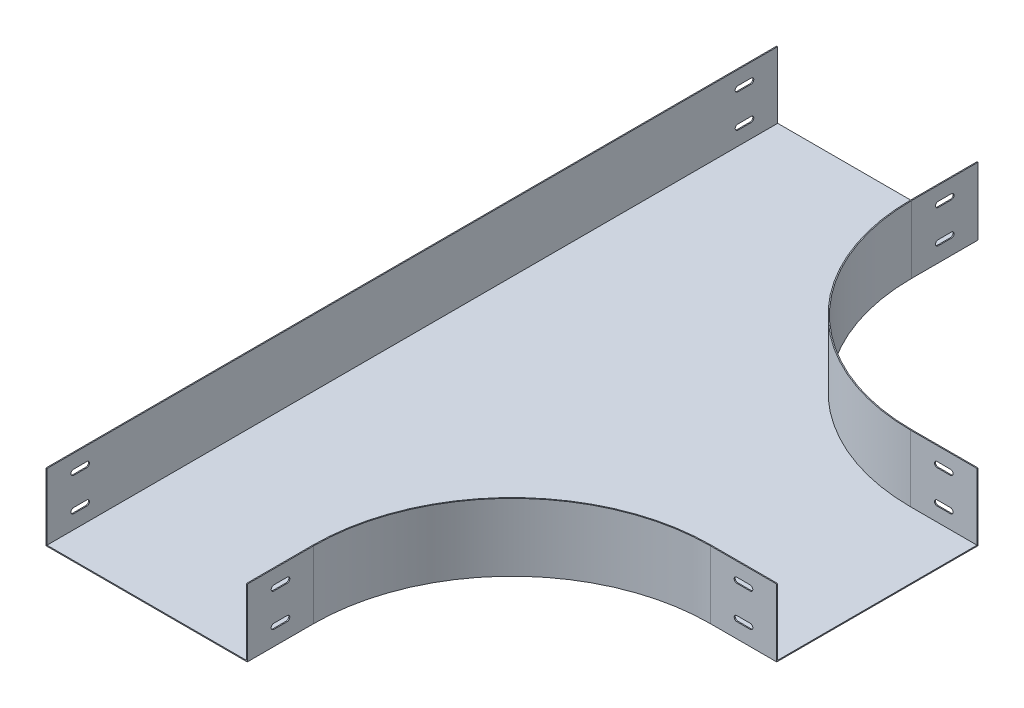
SolidWorks part; units mm, degrees
ref_plane "Front Plane" through (0, 0, 0) normal (0, 0, 1) x (1, 0, 0)
ref_plane "Top Plane" through (0, 0, 0) normal (0, 1, 0) x (1, 0, 0)
ref_plane "Right Plane" through (0, 0, 0) normal (1, 0, 0) x (0, 0, -1)
sketch "Sketch1" plane through (0, 0, 0) normal (0, 1, 0) x (1, 0, 0)
  line L0 (-150, 550) -> (150, 550)
  line L1 (-150, -550) -> (150, -550)
  line L2 (550, 150) -> (550, -150)
  line L3 (-150, 550) -> (-150, -550)
  line L4 (150, -550) -> (150, -450)
  line L5 (550, -150) -> (450, -150)
  line L6 (150, 550) -> (150, 450)
  line L7 (550, 0) -> (-150, 0) construction
  line L11 (550, 150) -> (450, 150)
  line L12 (0, 550) -> (0, -550) construction
  arc A2 (150, 450) -> (450, 150) centre (450, 450) ccw
  arc A3 (150, -450) -> (450, -150) centre (450, -450) cw
  dimension "Radius" = 300
  dimension "Width" = 300
  dimension "Length" = 1100
extrude "Boss-Extrude1" add sketch "Sketch1" against normal blind 1.5
sketch "Sketch2" plane through (0, 0, 0) normal (0, 1, 0) x (1, 0, 0)
  line L0 (150, -550) -> (150, -450) construction
  line L1 (450, -150) -> (550, -150) construction
  line L2 (150, -550) -> (150, -450)
  line L3 (450, -150) -> (550, -150)
  line L4 (-150, 550) -> (-150, -550)
  line L6 (550, 150) -> (450, 150) construction
  line L7 (150, 450) -> (150, 550) construction
  line L8 (550, 150) -> (450, 150)
  line L9 (150, 450) -> (150, 550)
  arc A0 (450, -150) -> (150, -450) centre (450, -450) ccw construction
  arc A1 (450, -150) -> (150, -450) centre (450, -450) ccw
  arc A2 (150, 450) -> (450, 150) centre (450, 450) ccw construction
  arc A3 (150, 450) -> (450, 150) centre (450, 450) ccw
extrude "Extrude-Thin1" add sketch "Sketch2" along normal blind 100 and the other way up to surface (1.5 mm away) thin other way up to face at (217.5736, -1.5, 0) thin type one direction wall 1.5
sketch "Sketch3" plane through (0, 0, 0) normal (0, 0, 1) x (1, 0, 0)
  line L0 (490, 75) -> (510, 75) construction
  line L1 (490, 79) -> (510, 79)
  line L2 (490, 71) -> (510, 71)
  line L3 (490, 25) -> (510, 25) construction
  line L4 (490, 29) -> (510, 29)
  line L5 (490, 21) -> (510, 21)
  line L6 (450, 50) -> (550, 50) construction
  line L7 (550, -1.5) -> (550, 100) construction
  line L9 (500, 0) -> (500, 50) construction
  line L11 (500, 50) -> (500, 100) construction
  arc A0 (490, 79) -> (490, 71) centre (490, 75) ccw
  arc A1 (510, 71) -> (510, 79) centre (510, 75) ccw
  arc A2 (490, 29) -> (490, 21) centre (490, 25) ccw
  arc A3 (510, 21) -> (510, 29) centre (510, 25) ccw
  point P2 (500, 75)
  point P8 (500, 25)
  dimension "D1" = 4
  dimension "D2" = 20
  dimension "D3" = 50
  dimension "D4" = 50
  dimension "D5" = 100
extrude "Cut-Extrude1" cut sketch "Sketch3" against normal through all and the other way through all
sketch "Sketch4" plane through (0, 0, 0) normal (1, 0, 0) x (0, 0, -1)
  line L0 (-550, 50) -> (-450, 50) construction
  line L1 (-550, -1.5) -> (-550, 100) construction
  line L2 (450, 50) -> (550, 50) construction
  line L3 (-500, 100) -> (-500, 50) construction
  line L4 (500, 100) -> (500, 50) construction
  line L5 (-500, 50) -> (-500, 0) construction
  line L6 (500, 50) -> (500, 0) construction
  line L7 (-510, 75) -> (-490, 75) construction
  line L8 (-510, 79) -> (-490, 79)
  line L9 (-510, 71) -> (-490, 71)
  line L10 (-510, 25) -> (-490, 25) construction
  line L11 (-510, 29) -> (-490, 29)
  line L12 (-510, 21) -> (-490, 21)
  line L13 (490, 75) -> (510, 75) construction
  line L14 (490, 79) -> (510, 79)
  line L15 (490, 71) -> (510, 71)
  line L16 (490, 25) -> (510, 25) construction
  line L17 (490, 29) -> (510, 29)
  line L18 (490, 21) -> (510, 21)
  line L19 (550, 100) -> (550, -1.5) construction
  arc A0 (-510, 79) -> (-510, 71) centre (-510, 75) ccw
  arc A1 (-490, 71) -> (-490, 79) centre (-490, 75) ccw
  arc A2 (-510, 29) -> (-510, 21) centre (-510, 25) ccw
  arc A3 (-490, 21) -> (-490, 29) centre (-490, 25) ccw
  arc A4 (490, 79) -> (490, 71) centre (490, 75) ccw
  arc A5 (510, 71) -> (510, 79) centre (510, 75) ccw
  arc A6 (490, 29) -> (490, 21) centre (490, 25) ccw
  arc A7 (510, 21) -> (510, 29) centre (510, 25) ccw
  point P15 (-500, 75)
  point P21 (-500, 25)
  point P29 (500, 75)
  point P35 (500, 25)
  dimension "D1" = 4
  dimension "D2" = 20
  dimension "D3" = 50
  dimension "D4" = 50
  dimension "D5" = 100
extrude "Cut-Extrude2" cut sketch "Sketch4" against normal through all and the other way through all
sketch "Sketch5" plane through (0, 0, 0) normal (0, 1, 0) x (1, 0, 0)
  line L0 (-150, -550) -> (150, -550) construction
  line L1 (550, -150) -> (550, 150) construction
  line L2 (150, 550) -> (-150, 550) construction
  point P0 (0, -550)
  point P1 (550, 0)
  point P4 (0, 550)
  point P10 (0, 0)
other "CPoint1" parameters "Diameter"=10, "StubLength"=300
ref_axis "Axis1" through (560, 0, 0) along (-1, 0, 0)
other "CPoint2" parameters "Diameter"=10, "StubLength"=300
ref_axis "Axis3" through (0, 0, 560) along (0, 0, -1)
other "CPoint3" parameters "Diameter"=10, "StubLength"=300
ref_axis "Axis4" through (0, 0, -560) along (0, 0, 1)
other "RPoint1"
equation "\"D5@Extrude-Thin1\"=\"Thickness@Boss-Extrude1\""
equation "\"D3@Sketch3\"=\"Height@Extrude-Thin1\"/2"
equation "\"D4@Sketch3\"=\"Height@Extrude-Thin1\"/2"
equation "\"D3@Sketch4\"=\"Height@Extrude-Thin1\"/2"
equation "\"D4@Sketch4\"=\"Height@Extrude-Thin1\"/2"
